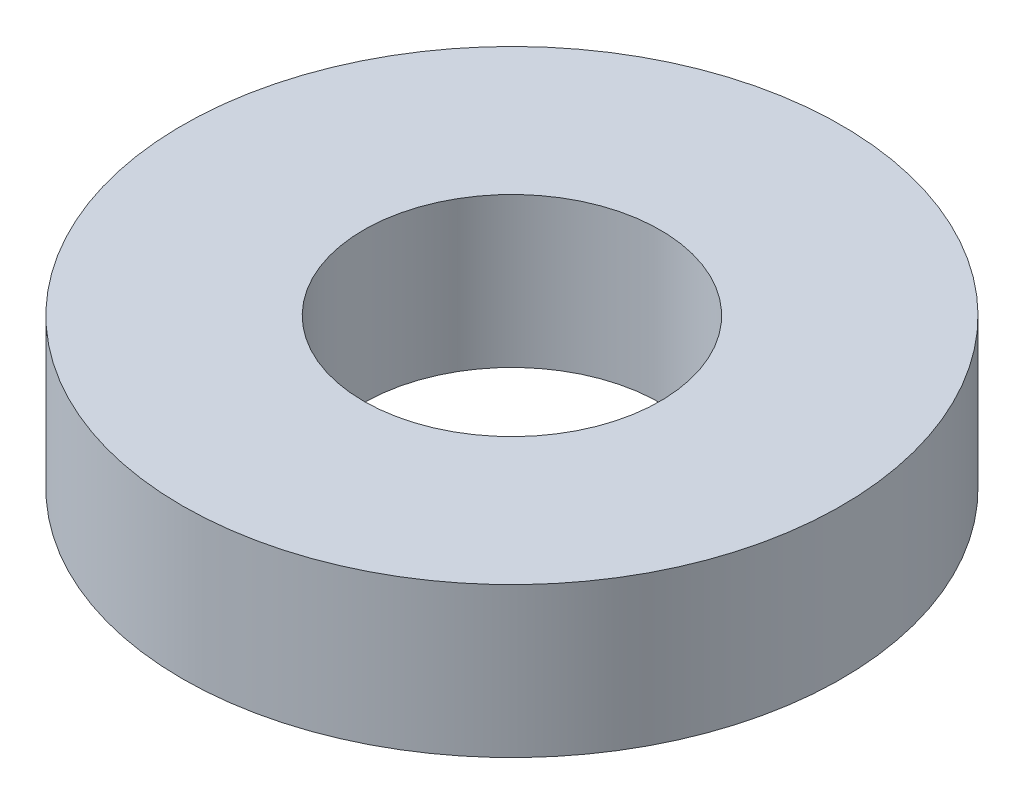
SolidWorks part; units mm, degrees
material "Galvanized Steel"
ref_plane "Front Plane" through (0, 0, 0) normal (0, 0, 1) x (1, 0, 0)
ref_plane "Top Plane" through (0, 0, 0) normal (0, 1, 0) x (1, 0, 0)
ref_plane "Right Plane" through (0, 0, 0) normal (1, 0, 0) x (0, 0, -1)
sketch "Sketch1" plane through (0, 0, 0) normal (0, 1, 0) x (1, 0, 0)
  circle A0 centre (0, 0) radius 11
  circle A1 centre (0, 0) radius 4.95
  dimension "D1" = 22
  dimension "D2" = 9.9
extrude "Boss-Extrude1" add sketch "Sketch1" along normal blind 5
